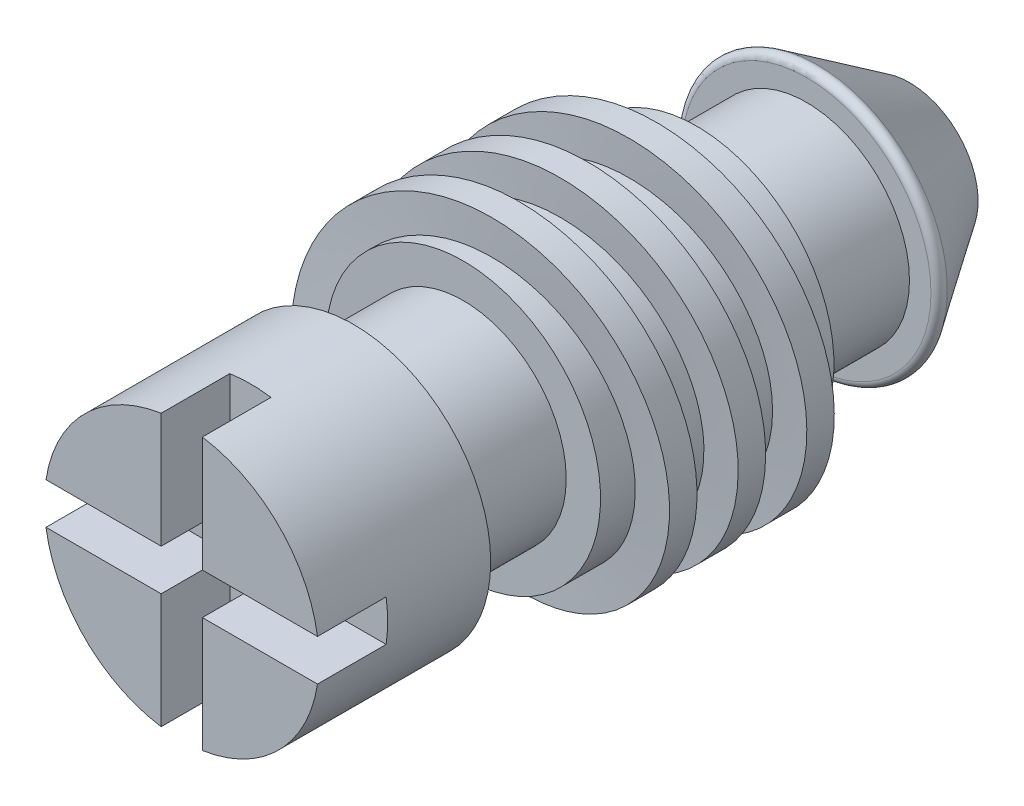
SolidWorks part; units mm, degrees
ref_plane "Front Plane" through (0, 0, 0) normal (0, 0, 1) x (1, 0, 0)
ref_plane "Top Plane" through (0, 0, 0) normal (0, 1, 0) x (1, 0, 0)
ref_plane "Right Plane" through (0, 0, 0) normal (1, 0, 0) x (0, 0, -1)
sketch "Sketch1" plane through (0, 0, 0) normal (0, 0, 1) x (1, 0, 0)
  circle A1 centre (0, 0) radius 1.5
  circle A2 centre (0, 0) radius 2
  dimension "D1" = 3
  dimension "D2" = 4
extrude "Boss-Extrude1" add sketch "Sketch1" along normal blind 2.5 contours A2
extrude "Boss-Extrude2" add sketch "Sketch1<3>" against normal blind 1.6 contours A1
sketch "Sketch1<3>" plane through (0, 0, 0) normal (0, 0, 1) x (1, 0, 0) same geometry as "Sketch1"
extrude "Boss-Extrude3" add sketch "Sketch1<4>" against normal blind 3.4 from surface contours A2 starting at face at (1.5, 0, -1.6)
sketch "Sketch1<4>" plane through (0, 0, 0) normal (0, 0, 1) x (1, 0, 0) same geometry as "Sketch1"
ref_plane "Plane1" through (0, 0, -4.8) normal (0, 0, -1) x (-1, 0, 0)
sketch "Sketch2" plane through (0, 0, -4.8) normal (0, 0, -1) x (-1, 0, 0)
  circle A0 centre (0, 0) radius 2.5
  dimension "D1" = 5
curve "Helix/Spiral1" pitch 1 height 3 radius 2.5 centre (0, 0, -4.8) axis (0, 0, 1) start towards (-1, 0, 0)
sketch "Sketch3" plane through (0, 0, 0) normal (0, 1, 0) x (1, 0, 0)
  line L1 (-2.5, 2) -> (-2, 2)
  line L2 (-2.5, 2) -> (-2.5, 1.6)
  line L3 (-2.5, 1.6) -> (-2, 1.6)
  line L4 (-2, 2) -> (-2, 1.6)
  dimension "D1" = 0.4
  dimension "D2" = 0.5
sweep "Sweep1" add profiles "Sketch3" path "Helix/Spiral1"
extrude "Boss-Extrude4" add sketch "Sketch1<5>" against normal blind 1.6 from surface contours A1 starting at face at (-2, 0, -5)
sketch "Sketch1<5>" plane through (0, 0, 0) normal (0, 0, 1) x (1, 0, 0) same geometry as "Sketch1"
sketch "Sketch4" plane through (0, 0, 0) normal (0, 1, 0) x (1, 0, 0)
  line L0 (0, 9.4678) -> (0, 0) construction
  line L1 (0, 6.6) -> (2, 6.6)
  line L2 (1.5, 6.6) -> (-1.5, 6.6) construction
  line L3 (2, 6.6) -> (1, 8.1)
  line L4 (1, 8.1) -> (0, 8.1)
  line L5 (0, 8.1) -> (0, 6.6)
  dimension "D1" = 2
  dimension "D2" = 1.5
  dimension "D3" = 1
revolve "Revolve1" add sketch "Sketch4" angle 360 about L0
fillet "Fillet1" radius 0.1 1 edges at (-2, 0, -6.6)
sketch "Sketch5" plane through (0, 0, 2.5) normal (0, 0, 1) x (1, 0, 0)
  line L0 (0, 2) -> (0, -2) construction
  line L1 (-2, 0) -> (2, 0) construction
  line L2 (0.3, 1.9774) -> (0.3, 0.3)
  line L3 (-1.9774, 0.3) -> (-0.3, 0.3)
  line L4 (-0.3, 1.9774) -> (-0.3, 0.3)
  line L5 (-1.9774, -0.3) -> (-0.3, -0.3)
  line L6 (0.3, 0.3) -> (1.9774, 0.3)
  line L7 (-0.3, -0.3) -> (-0.3, -1.9774)
  line L8 (0.3, -0.3) -> (1.9774, -0.3)
  line L9 (0.3, -0.3) -> (0.3, -1.9774)
  circle A0 centre (0, 0) radius 2 construction
  arc A1 (0.3, 1.9774) -> (-0.3, 1.9774) centre (0, 0) ccw
  arc A2 (-1.9774, 0.3) -> (-1.9774, -0.3) centre (0, 0) ccw
  arc A3 (1.9774, -0.3) -> (1.9774, 0.3) centre (0, 0) ccw
  arc A4 (-0.3, -1.9774) -> (0.3, -1.9774) centre (0, 0) ccw
  dimension "D1" = 0.3
  dimension "D2" = 0.3
extrude "Cut-Extrude1" cut sketch "Sketch5" against normal blind 1
